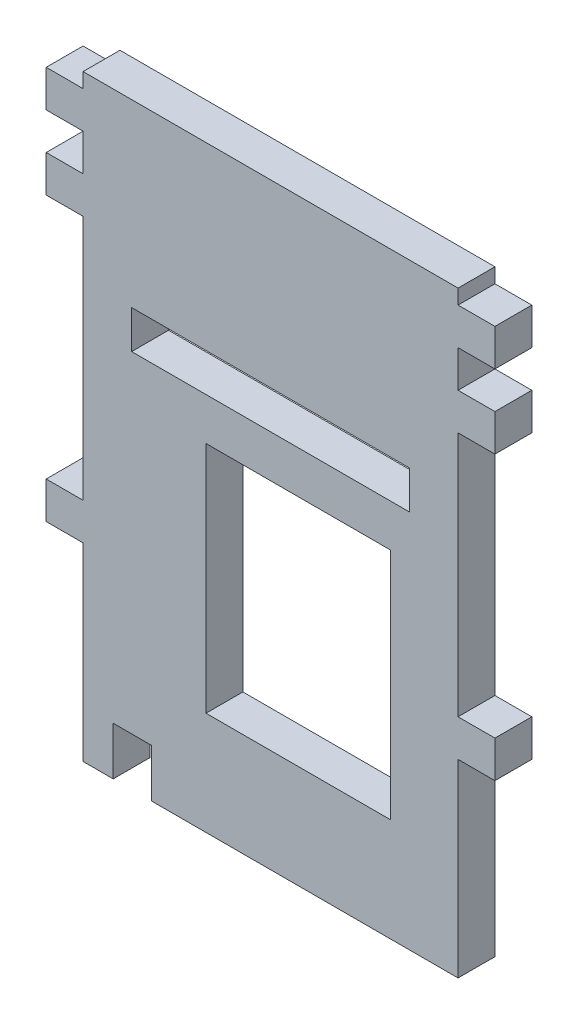
SolidWorks part; units mm, degrees
ref_plane "Ebene vorne (XY)" through (0, 0, 0) normal (0, 0, 1) x (1, 0, 0)
ref_plane "Ebene oben  (XZ)" through (0, 0, 0) normal (0, 1, 0) x (1, 0, 0)
ref_plane "Ebene rechts  (YZ)" through (0, 0, 0) normal (1, 0, 0) x (0, 0, -1)
ref_axis "x-Achse" through (-4.825, 0, 0) along (1, 0, 0)
ref_axis "y-Achse" through (0, 8.63, 0) along (0, -1, 0)
ref_axis "z-Achse" through (0, 0, -0.15) along (0, 0, 1)
sketch "Profile_Laser_profile_3mm" plane through (0, 0, 0) normal (0, 0, 1) x (1, 0, 0)
  line L0 (0, -42.4) -> (2.45, -42.4)
  line L1 (2.45, -42.4) -> (2.45, -38.48)
  line L2 (2.45, -38.48) -> (5.55, -38.48)
  line L3 (5.55, -38.48) -> (5.55, -42.4)
  line L4 (5.55, -42.4) -> (30.5, -42.4)
  line L5 (30.5, -42.4) -> (30.5, -27)
  line L6 (30.5, -27) -> (33.5, -27)
  line L7 (33.5, -27) -> (33.5, -24)
  line L8 (33.5, -24) -> (30.5, -24)
  line L9 (30.5, -24) -> (30.5, -4)
  line L10 (30.5, -4) -> (33.5, -4)
  line L11 (33.5, -4) -> (33.5, -1)
  line L12 (33.5, -1) -> (30.5, -1)
  line L13 (30.5, -1) -> (30.5, 2)
  line L14 (30.5, 2) -> (33.5, 2)
  line L15 (33.5, 2) -> (33.5, 5)
  line L16 (33.5, 5) -> (30.5, 5)
  line L17 (30.5, 5) -> (30.5, 6.2)
  line L18 (30.5, 6.2) -> (0, 6.2)
  line L19 (0, 6.2) -> (0, 5)
  line L20 (0, 5) -> (-3, 5)
  line L21 (-3, 5) -> (-3, 2)
  line L22 (-3, 2) -> (0, 2)
  line L23 (0, 2) -> (0, -1)
  line L24 (0, -1) -> (-3, -1)
  line L25 (-3, -1) -> (-3, -4)
  line L26 (-3, -4) -> (0, -4)
  line L27 (0, -4) -> (0, -24)
  line L28 (0, -24) -> (-3, -24)
  line L29 (-3, -24) -> (-3, -27)
  line L30 (-3, -27) -> (0, -27)
  line L31 (0, -27) -> (0, -42.4)
  line L32 (3.95, -11.55) -> (26.55, -11.55)
  line L33 (26.55, -11.55) -> (26.55, -8.45)
  line L34 (26.55, -8.45) -> (3.95, -8.45)
  line L35 (3.95, -8.45) -> (3.95, -11.55)
  line L36 (10, -34) -> (25, -34)
  line L37 (25, -34) -> (25, -15)
  line L38 (25, -15) -> (10, -15)
  line L39 (10, -15) -> (10, -34)
extrude "Laser_profile_3mm" add sketch "Profile_Laser_profile_3mm" along normal blind 3
